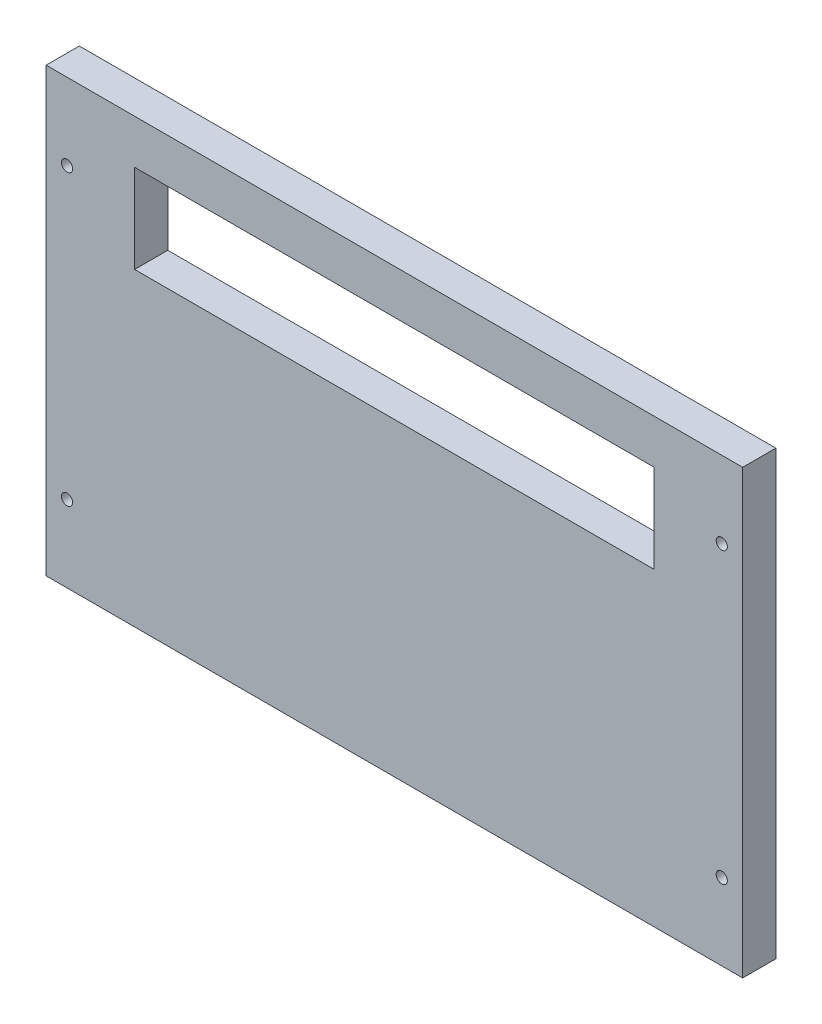
SolidWorks part; units mm, degrees
ref_plane "Front Plane" through (0, 0, 0) normal (0, 0, 1) x (1, 0, 0)
ref_plane "Top Plane" through (0, 0, 0) normal (0, 1, 0) x (1, 0, 0)
ref_plane "Right Plane" through (0, 0, 0) normal (1, 0, 0) x (0, 0, -1)
sketch "Sketch1" plane through (0, 0, 0) normal (0, 0, 1) x (1, 0, 0)
  line L1 (0, 0) -> (200, 0)
  line L2 (0, 0) -> (0, 127)
  line L3 (0, 127) -> (200, 127)
  line L4 (200, 0) -> (200, 127)
  circle A3 centre (6, 105) radius 1.6
  circle A4 centre (6, 22) radius 1.6
  circle A5 centre (194, 22) radius 1.6
  circle A6 centre (194, 105) radius 1.6
  dimension "D11" = 3.2
  dimension "D14" = 3.2
  dimension "D17" = 3.2
  dimension "D22" = 3.2
  dimension "D1" = 127
  dimension "D2" = 200
  dimension "D12" = 6
  dimension "D13" = 22
  dimension "D15" = 6
  dimension "D16" = 22
  dimension "D18" = 6
  dimension "D19" = 22
  dimension "D20" = 6
  dimension "D21" = 22
extrude "Wall" add sketch "Sketch1" along normal blind 9.525
sketch "Sketch2" plane through (0, 0, 9.525) normal (0, 0, 1) x (1, 0, 0)
  line L0 (100, 127) -> (100, 98.425) construction
  line L1 (200, 127) -> (0, 127) construction
  line L2 (100, 98.425) -> (66.6667, 98.425) construction
  line L3 (100, 98.425) -> (133.3333, 98.425) construction
  line L4 (0, 127) -> (0, 0) construction
  circle A0 centre (100, 98.425) radius 3.9687
  circle A1 centre (66.6667, 98.425) radius 3.9688
  circle A2 centre (133.3333, 98.425) radius 3.9687
  dimension "D2" = 7.9375
  dimension "D1" = 28.575
  dimension "D3" = 66.6667
extrude "RodSupportCutouts" [suppressed] cut sketch "Sketch2" against normal up to next
sketch "Sketch3" plane through (0, 0, 9.525) normal (0, 0, 1) x (1, 0, 0)
  line L1 (25.4, 88.9) -> (174.6, 88.9)
  line L2 (25.4, 88.9) -> (25.4, 114.3)
  line L3 (25.4, 114.3) -> (174.6, 114.3)
  line L4 (174.6, 88.9) -> (174.6, 114.3)
  line L5 (25.4, 88.9) -> (174.6, 114.3) construction
  line L6 (25.4, 114.3) -> (174.6, 88.9) construction
  line L7 (200, 127) -> (0, 127) construction
  line L8 (0, 127) -> (0, 0) construction
  point P0 (100, 101.6)
  point P9 (100, 127)
  dimension "D1" = 25.4
  dimension "D2" = 25.4
  dimension "D3" = 25.4
extrude "CannulaLargeCutout" cut sketch "Sketch3" against normal up to next
sketch "Sketch4" [suppressed] plane through (0, 0, 9.525) normal (0, 0, 1) x (1, 0, 0)
  line L0 (6, 103.5) -> (194, 103.5) construction
  line L1 (6, 105) -> (6, 22) construction
  line L2 (194, 105) -> (194, 22) construction
  line L3 (200, 127) -> (0, 127) construction
  line L4 (0, 127) -> (0, 0) construction
  circle A0 centre (60, 103.5) radius 6.35
  circle A1 centre (20, 103.5) radius 6.35
  circle A2 centre (100, 103.5) radius 6.35
  circle A3 centre (140, 103.5) radius 6.35
  circle A4 centre (60, 63.5) radius 6.35
  circle A5 centre (100, 63.5) radius 6.35
  circle A6 centre (140, 63.5) radius 6.35
  circle A7 centre (60, 23.5) radius 6.35
  circle A8 centre (100, 23.5) radius 6.35
  circle A9 centre (140, 23.5) radius 6.35
  circle A10 centre (20, 63.5) radius 6.35
  circle A11 centre (20, 23.5) radius 6.35
  circle A12 centre (180, 103.5) radius 6.35
  circle A13 centre (180, 63.5) radius 6.35
  circle A14 centre (180, 23.5) radius 6.35
  point P42 (100, 127)
  point P45 (0, 63.5)
  dimension "D3" = 12.7
  dimension "D1" = 5
  dimension "D2" = 3
extrude "CannulaHoles" [suppressed] cut sketch "Sketch4" against normal up to next
equation "\"Length\"= 283mm"
equation "\"Width\"= 225mm"
equation "\"WallThickness\"= 12.5mm"
equation "\"UpperWaterJacketThickness\"= 28mm"
equation "\"SpacerHeight\"= 80.2mm"
equation "\"SpacerCornerWidth\"= 10mm"
equation "\"SpacerCornerHeight\"= 60.16mm"
equation "\"SpacerPegDiameter\"= 10mm"
equation "\"SpacerPegHeight\"= 10mm"
equation "\"TubingShort\"= 110mm"
equation "\"TubingLong\"= 175mm"
equation "\"PlateLength\"= 252mm"
equation "\"PlateWidth\"= 190mm"
equation "\"PlateHoleDiameter\"= 5.9mm"
equation "\"PlateHoleBottom\"= 2mm"
equation "\"PlateHoleSide\"= 1.55mm"
equation "\"PlateHoleSpacing\"= 3.1mm"
equation "\"PlateThickness\"= 1.55mm"
equation "\"ReservoirBottom\"= 12.5mm"
equation "\"ReservoirSupportWidth\"= 12mm"
equation "\"ReservoirSupportHeight\"= 15.1mm"
equation "\"ReservoirSupportPlacementHeight\"= 50mm"
equation "\"ReservoirHoleDiameter\"= 12.7mm"
equation "\"ReservoirHoleRight\"= 25mm"
equation "\"ReservoirHoleTop\"= \"ReservoirSupportPlacementHeight\""
equation "\"ReservoirHeight\"= 90mm"
equation "\"ReservoirPortBottom\"= 4mm"
equation "\"ReservoirPortTop\"= 10mm"
equation "\"ReservoirPortWidth\"= 101mm"
equation "\"CustomSpacerWallThickness\"= 0.375in"
equation "\"CustomSpacerHeight\"= 5in"
equation "\"CustomSpacerRodHoleHeight\"= .75in"
equation "\"CustomSpacerRodHoleDiameter\"= .3125in"
equation "\"ScrewBlockSide\"= 12mm"
equation "\"ScrewBlockUpperHeight\"= 16mm"
equation "\"ScrewBlockLowerHeight\"= 16mm"
equation "\"InternalLength\"= \"Length\" - ( 2 * \"WallThickness\" )"
equation "\"InternalWidth\"= \"Width\" - ( 2 * \"WallThickness\" )"
equation "\"CustomSpacerPegHeight\"= 1in"
equation "\"CustomSpacerScrewBore\"=3.2mm"
equation "\"CustomSpacerScrewDepth\"=10mm"
equation "\"D1@Sketch1\"=\"CustomSpacerHeight\""
equation "\"D2@Sketch1\"=\"WallLength\""
equation "\"D11@Sketch1\"=\"CustomSpacerScrewBore\""
equation "\"D12@Sketch1\"=\"ScrewBlockSide\"/2"
equation "\"D13@Sketch1\"=\"ScrewBlockUpperHeight\"+\"ScrewBlockSide\"/2"
equation "\"D14@Sketch1\"=\"CustomSpacerScrewBore\""
equation "\"D15@Sketch1\"=\"ScrewBlockSide\"/2"
equation "\"D16@Sketch1\"=\"ScrewBlockLowerHeight\"+\"ScrewBlockSide\"/2"
equation "\"D17@Sketch1\"=\"CustomSpacerScrewBore\""
equation "\"D18@Sketch1\"=\"ScrewBlockSide\"/2"
equation "\"D19@Sketch1\"=\"ScrewBlockUpperHeight\"+\"ScrewBlockSide\"/2"
equation "\"D20@Sketch1\"=\"ScrewBlockSide\"/2"
equation "\"D21@Sketch1\"=\"ScrewBlockLowerHeight\"+\"ScrewBlockSide\"/2"
equation "\"D22@Sketch1\"=\"CustomSpacerScrewBore\""
equation "\"D1@Wall\" = \"CustomSpacerWallThickness\""
equation "\"D1@Sketch2\"=\"CustomSpacerRodHoleHeight\" + \"CustomSpacerRodHoleDiameter\" +0.0625in"
equation "\"D2@Sketch2\"=\"CustomSpacerRodHoleDiameter\""
equation "\"D3@Sketch2\"=\"InternalWidth\" / 3"
equation "\"D1@Sketch3\"=1in"
equation "\"WallLength\"= \"InternalWidth\""
